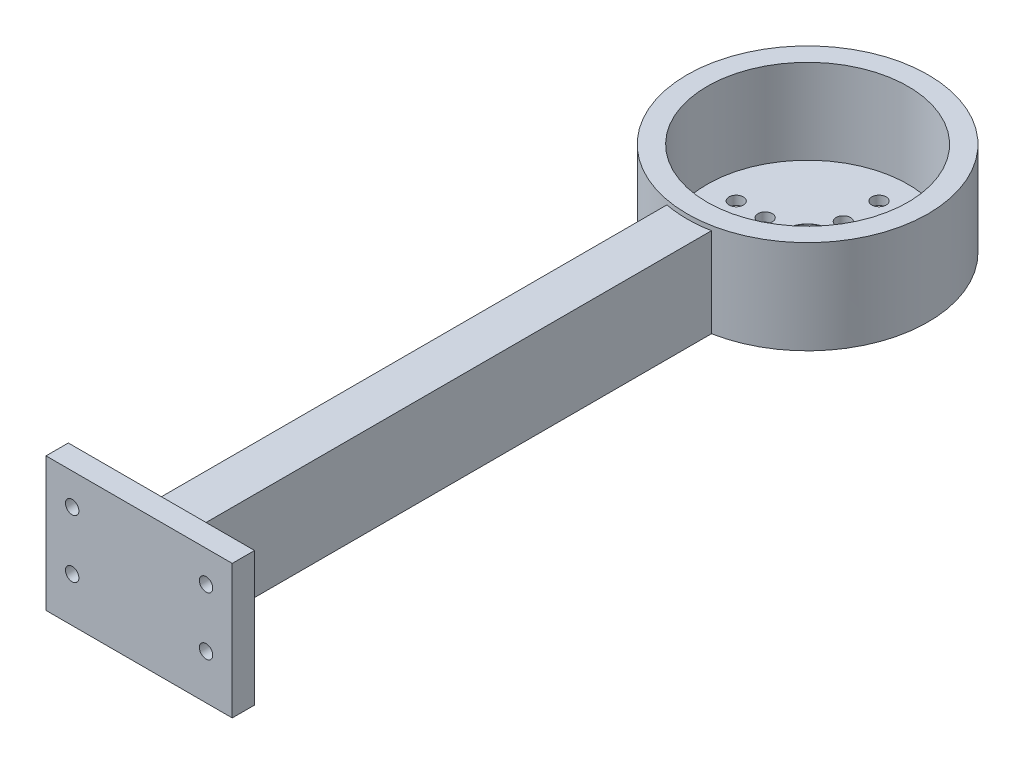
SolidWorks part; units mm, degrees
ref_plane "Front Plane" through (0, 0, 0) normal (0, 0, 1) x (1, 0, 0)
ref_plane "Top Plane" through (0, 0, 0) normal (0, 1, 0) x (1, 0, 0)
ref_plane "Right Plane" through (0, 0, 0) normal (1, 0, 0) x (0, 0, -1)
sketch "Sketch1" plane through (0, 0, 0) normal (0, 0, 1) x (1, 0, 0)
  line L1 (-20.865, 15) -> (20.865, 15)
  line L2 (-20.865, 15) -> (-20.865, -15)
  line L3 (-20.865, -15) -> (20.865, -15)
  line L4 (20.865, 15) -> (20.865, -15)
  line L5 (-20.865, 15) -> (20.865, -15) construction
  line L6 (-20.865, -15) -> (20.865, 15) construction
  point P0 (0, 0)
  dimension "D1" = 41.73
  dimension "D2" = 30
extrude "Boss-Extrude1" add sketch "Sketch1" along normal blind 5
sketch "Sketch2" plane through (0, 0, 0) normal (0, 0, -1) x (-1, 0, 0)
  line L1 (-5, 10) -> (5, 10)
  line L2 (-5, 10) -> (-5, -10)
  line L3 (-5, -10) -> (5, -10)
  line L4 (5, 10) -> (5, -10)
  line L5 (-5, 10) -> (5, -10) construction
  line L6 (-5, -10) -> (5, 10) construction
  point P0 (0, 0)
  dimension "D1" = 20
  dimension "D2" = 10
extrude "Boss-Extrude3" add sketch "Sketch2" along normal blind 144.78
sketch "Sketch3" plane through (0, 10, 0) normal (0, 1, 0) x (1, 0, 0)
  line L0 (-5, 144.78) -> (5, 144.78) construction
  circle A0 centre (0, 144.78) radius 22.5
  circle A1 centre (0, 144.78) radius 27
  dimension "D1" = 45
  dimension "D2" = 54
extrude "Boss-Extrude5" add sketch "Sketch3" along normal blind 1 and the other way blind 8
sketch "Sketch4" plane through (0, 10, 0) normal (0, 1, 0) x (1, 0, 0)
  line L0 (-5, 144.78) -> (5, 144.78) construction
  circle A0 centre (0, 144.78) radius 22.5
  circle A1 centre (0, 144.78) radius 22.5 construction
extrude "Cut-Extrude3" cut sketch "Sketch4" against normal through all
sketch "Sketch7" plane through (0, 10, 0) normal (0, 1, 0) x (1, 0, 0)
  circle A0 centre (0, 144.78) radius 27
  circle A1 centre (0, 144.78) radius 27 construction
extrude "Boss-Extrude6" add sketch "Sketch7" against normal up to vertex (20 mm away) up to point (5, -10, -122.8426)
extrude "Cut-Extrude5" cut sketch "Sketch4<2>" against normal blind 18
sketch "Sketch4<2>" plane through (0, 10, 0) normal (0, 1, 0) x (1, 0, 0) same geometry as "Sketch4"
hole_wizard "Ø3.0mm Dowel Hole3" positions "Sketch8" profile "Sketch9" hole size "Ø3.0" standard "DIN" end condition through all
sketch "Sketch8" plane through (0, 0, 0) normal (0, 0, -1) x (-1, 0, 0)
  line L0 (0, 15) -> (0, -15) construction
  line L1 (-20.865, 15) -> (20.865, 15) construction
  line L2 (20.865, -15) -> (-20.865, -15) construction
  point P0 (15, 8)
  point P2 (-15, 8)
  point P4 (15, -5)
  point P6 (-15, -5)
  dimension "D1" = 30
  dimension "D2" = 7
  dimension "D3" = 10
sketch "Sketch9" plane through (-15, 8, 0) normal (1, 0, 0) x (0, 1, 0)
  line L0 (0, 0) -> (0, 5)
  line L1 (0, 5) -> (1.5, 5)
  line L2 (1.5, 5) -> (1.5, 0.025)
  line L3 (1.5, 0.025) -> (1.525, 0)
  line L5 (1.525, 0) -> (0, 0)
  line L6 (-1.5, 0.025) -> (-1.525, 0) construction
  line L11 (0, -6.35) -> (0, 107.95) construction
  dimension "Thru Hole Dia." = 3
  dimension "Thru Hole Depth" = 5
  dimension "Near C'Sink Dia." = 3.05
  dimension "Near C'Sink Angle" = 90
hole_wizard "Ø10.0mm Dowel Hole1" positions "Sketch13" profile "Sketch14" hole size "Ø10.0" standard "DIN" end condition through all
sketch "Sketch13" plane through (0, -8, 0) normal (0, 1, 0) x (1, 0, 0)
  point P0 (0, 144.78)
sketch "Sketch14" plane through (0, -8, -144.78) normal (1, 0, 0) x (0, 0, 1)
  line L0 (0, 0) -> (0, 7)
  line L1 (0, 7) -> (5, 7)
  line L2 (5, 7) -> (5, 0.025)
  line L3 (5, 0.025) -> (5.025, 0)
  line L5 (5.025, 0) -> (0, 0)
  line L6 (-5, 0.025) -> (-5.025, 0) construction
  line L11 (0, -6.35) -> (0, 107.95) construction
  dimension "Thru Hole Dia." = 10
  dimension "Thru Hole Depth" = 7
  dimension "Near C'Sink Dia." = 10.05
  dimension "Near C'Sink Angle" = 90
hole_wizard "Ø3.0mm Dowel Hole4" positions "Sketch15" profile "Sketch17" hole size "Ø3.0" standard "DIN" end condition through all
sketch "Sketch15" plane through (0, -8, 0) normal (0, 1, 0) x (1, 0, 0)
  circle A1 centre (0, 144.78) radius 16 construction
  point P0 (0, 128.78)
  point P2 (0, 136.78)
  point P4 (16, 144.78)
  point P6 (9.5, 144.78)
  point P8 (0, 160.78)
  point P10 (0, 152.78)
  point P12 (-16, 144.78)
  point P14 (-9.5, 144.78)
  dimension "D1" = 16
  dimension "D2" = 8
  dimension "34" = 32
  dimension "D3" = 19
  dimension "D4" = 9.5
sketch "Sketch17" plane through (0, -8, -128.78) normal (1, 0, 0) x (0, 0, 1)
  line L0 (0, 0) -> (0, 7)
  line L1 (0, 7) -> (1.6, 7)
  line L2 (1.6, 7) -> (1.6, 0)
  line L5 (1.6, 0) -> (0, 0)
  line L11 (0, -6.35) -> (0, 107.95) construction
  dimension "Thru Hole Dia." = 3.2
  dimension "Thru Hole Depth" = 7
